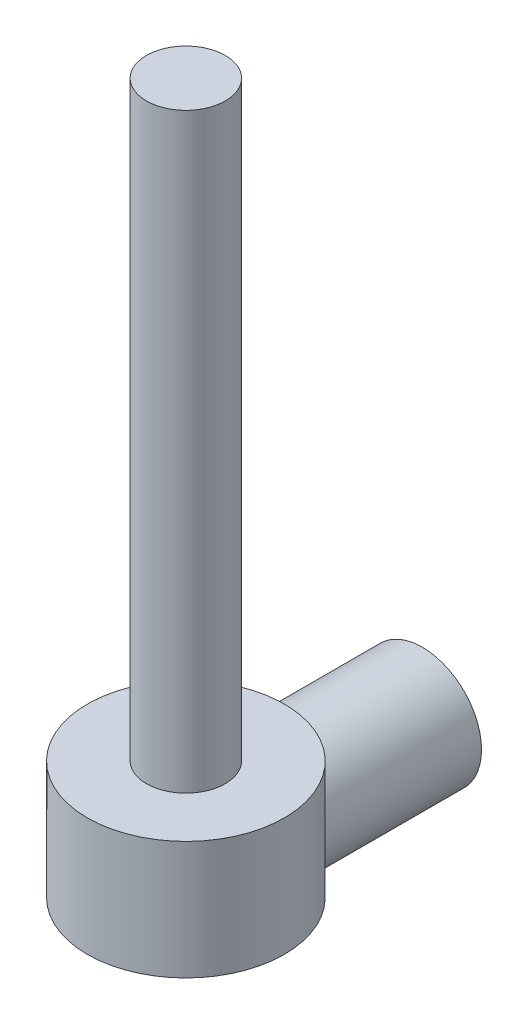
SolidWorks part; units mm, degrees
ref_plane "Front Plane" through (0, 0, 0) normal (0, 0, 1) x (1, 0, 0)
ref_plane "Top Plane" through (0, 0, 0) normal (0, 1, 0) x (1, 0, 0)
ref_plane "Right Plane" through (0, 0, 0) normal (1, 0, 0) x (0, 0, -1)
sketch "Sketch1" plane through (0, 0, 0) normal (0, 0, 1) x (1, 0, 0)
  circle A0 centre (0, 0) radius 30
  dimension "D1" = 60
extrude "Boss-Extrude1" add sketch "Sketch1" against normal blind 120
ref_axis "Axis1" through (-33, 0, 0) along (1, 0, 0)
ref_plane "Plane1" through (0, 0, 0) normal (0, 1, 0) x (1, 0, 0)
sketch "Sketch2" plane through (0, 0, 0) normal (0, 1, 0) x (1, 0, 0)
  circle A0 centre (0, 0) radius 50
  dimension "D1" = 100
extrude "Boss-Extrude2" add sketch "Sketch2" along normal blind 40 and the other way blind 20
sketch "Sketch3" plane through (0, 40, 0) normal (0, 1, 0) x (1, 0, 0)
  circle A0 centre (0, 0) radius 20
  dimension "D1" = 40
extrude "Boss-Extrude3" add sketch "Sketch3" along normal blind 300
